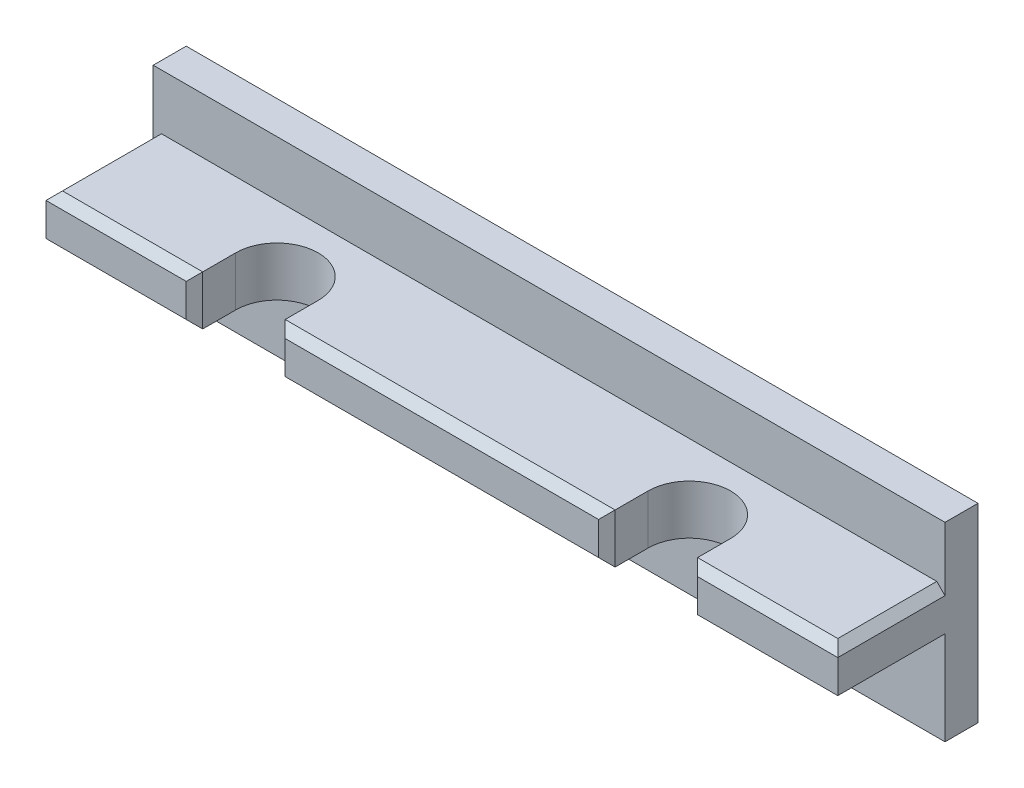
SolidWorks part; units mm, degrees
ref_plane "Front Plane" through (0, 0, 0) normal (0, 0, 1) x (1, 0, 0)
ref_plane "Top Plane" through (0, 0, 0) normal (0, 1, 0) x (1, 0, 0)
ref_plane "Right Plane" through (0, 0, 0) normal (1, 0, 0) x (0, 0, -1)
sketch "Sketch1" plane through (0, 0, 0) normal (0, 0, 1) x (1, 0, 0)
  line L0 (-24, 0) -> (24, 0)
  line L1 (24, 0) -> (24, 11.525)
  line L2 (24, 11.525) -> (-24, 11.525)
  line L3 (-24, 11.525) -> (-24, 0)
  line L4 (-24, 8.175) -> (24, 8.175)
  line L5 (-24, 5.175) -> (24, 5.175)
  point P5 (0, 0)
  dimension "D1" = 48
  dimension "D2" = 11.525
  dimension "D3" = 3
  dimension "D4" = 5.175
extrude "Boss-Extrude1" add sketch "Sketch1" along normal blind 2 contours L5 L3 L0 L1 | L3 L5 L1 L4 | L3 L4 L1 L2 region at (0, 2.5875, 0) region at (0, 6.675, 0) region at (0, 9.85, 0)
extrude "Boss-Extrude2" add sketch "Sketch1<3>" along normal blind 8.5 contours L3 L5 L1 L4 region at (0, 6.675, 0)
sketch "Sketch1<3>" plane through (0, 0, 0) normal (0, 0, 1) x (1, 0, 0) same geometry as "Sketch1"
sketch "Sketch2" plane through (0, 8.175, 0) normal (0, 1, 0) x (1, 0, 0)
  line L0 (0, 10.3894) -> (0, -15.1973) construction
  line L1 (24, -2) -> (-24, -2) construction
  line L2 (-15, -6) -> (-15, -8.5)
  line L3 (-24, -8.5) -> (24, -8.5) construction
  line L4 (-15, -8.5) -> (-10, -8.5)
  line L5 (-10, -8.5) -> (-10, -6)
  line L6 (10, -8.5) -> (10, -6)
  line L7 (15, -8.5) -> (10, -8.5)
  line L8 (15, -6) -> (15, -8.5)
  arc A0 (-10, -6) -> (-15, -6) centre (-12.5, -6) ccw
  arc A1 (10, -6) -> (15, -6) centre (12.5, -6) cw
  dimension "D3" = 5
  dimension "D1" = 12.5
  dimension "D2" = 4
extrude "Cut-Extrude1" cut sketch "Sketch2" against normal through all
chamfer "Chamfer1" distance 0.5 angle 45 14 edges at (-24, 5.175, 5.25) (-19.5, 5.175, 8.5) (-15, 6.675, 8.5) (-24, 8.175, 5.25) (-19.5, 8.175, 8.5) (10, 6.675, 8.5) (0, 5.175, 8.5) (-10, 6.675, 8.5) (0, 8.175, 8.5) (24, 5.175, 5.25) (19.5, 5.175, 8.5) (15, 6.675, 8.5) (19.5, 8.175, 8.5) (24, 8.175, 5.25)
equation "\"D3@Sketch1\"=3.175 - 0.175"
